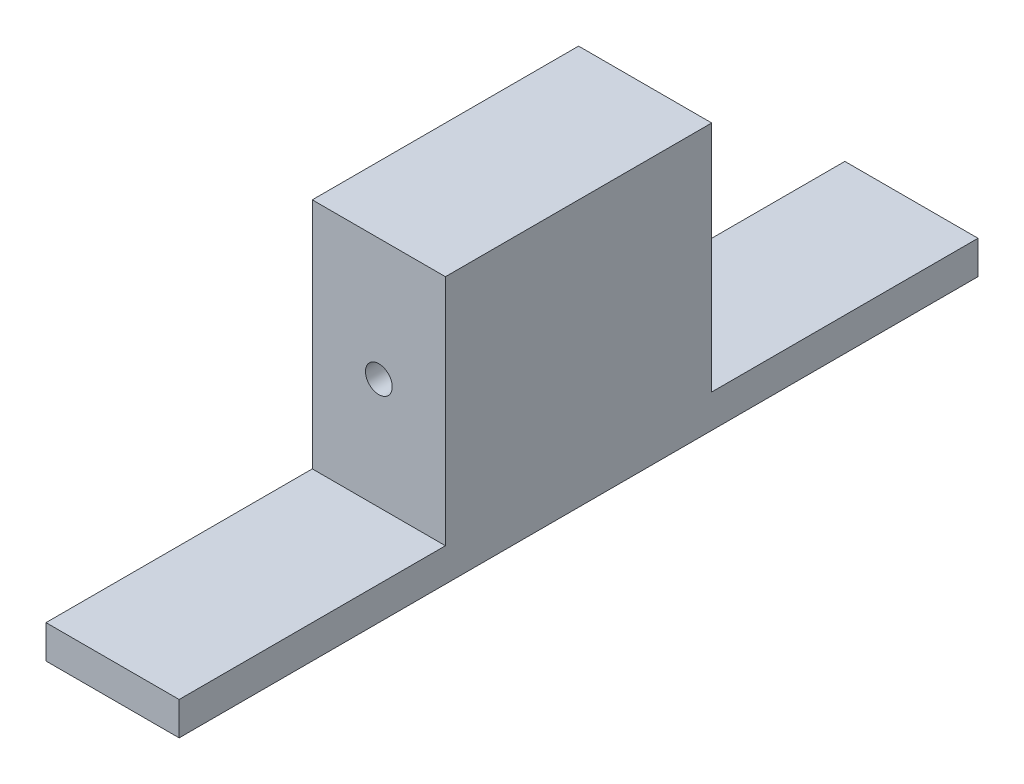
SolidWorks part; units mm, degrees
ref_plane "Front Plane" through (0, 0, 0) normal (0, 0, 1) x (1, 0, 0)
ref_plane "Top Plane" through (0, 0, 0) normal (0, 1, 0) x (1, 0, 0)
ref_plane "Right Plane" through (0, 0, 0) normal (1, 0, 0) x (0, 0, -1)
sketch "Sketch-Profile" plane through (0, 0, 0) normal (1, 0, 0) x (0, 0, -1)
  line L0 (-76.2, 6.35) -> (-76.2, 0)
  line L5 (-76.2, 6.35) -> (-25.4, 6.35)
  line L6 (-76.2, 0) -> (76.2, 0)
  line L7 (76.2, 6.35) -> (76.2, 0)
  line L8 (-76.2, 6.35) -> (76.2, 0) construction
  line L9 (-76.2, 0) -> (76.2, 6.35) construction
  line L10 (-25.4, 50.8) -> (-25.4, 6.35)
  line L11 (-25.4, 50.8) -> (25.4, 50.8)
  line L13 (25.4, 50.8) -> (25.4, 6.35)
  line L14 (-25.4, 50.8) -> (25.4, 6.35) construction
  line L15 (-25.4, 6.35) -> (25.4, 50.8) construction
  line L16 (25.4, 6.35) -> (76.2, 6.35)
  point P0 (0, 0)
  point P1 (0, 3.175)
  point P2 (0, 28.575)
  dimension "D1" = 6.35
  dimension "D2" = 50.8
  dimension "D3" = 152.4
  dimension "D4" = 50.8
extrude "Boss-Extrude1" add sketch "Sketch-Profile" along normal blind 25.4
sketch "Sketch-Hole Location" plane through (0, 0, 25.4) normal (0, 0, 1) x (1, 0, 0)
  line L0 (12.7, 0) -> (12.7, 50.8) construction
  line L1 (25.4, 0) -> (0, 0) construction
  line L2 (25.4, 50.8) -> (0, 50.8) construction
  line L3 (161.1833, 27.5181) -> (74.7483, 27.5181) construction
  point P6 (12.7, 27.5181)
  point P7 (0, 0)
sketch "Sketch5" plane through (0, 0, 25.4) normal (0, 0, 1) x (1, 0, 0)
  point P0 (12.7, 27.5181)
hole_wizard "1/4-20 Tapped Hole1" positions "Sketch5" profile "Sketch4" tap size "1/4-20" standard "ANSI Inch"
sketch "Sketch4" plane through (12.7, 27.5181, 25.4) normal (1, 0, 0) x (0, -1, 0)
  line L0 (0, 0) -> (0, 26.9338)
  line L1 (0, 26.9338) -> (2.5527, 25.4)
  line L2 (2.5527, 25.4) -> (2.5527, 0)
  line L5 (2.5527, 0) -> (0, 0)
  line L10 (0, 26.9338) -> (-2.5527, 25.4) construction
  line L11 (0, -6.35) -> (0, 107.95) construction
  dimension "Tap Drill Dia." = 5.1054
  dimension "Tap Drill Depth" = 25.4
  dimension "Drill Angle" = 118
cosmetic thread "Hole Thread1" parameters "D1"=25.4, "D2"=6.35
